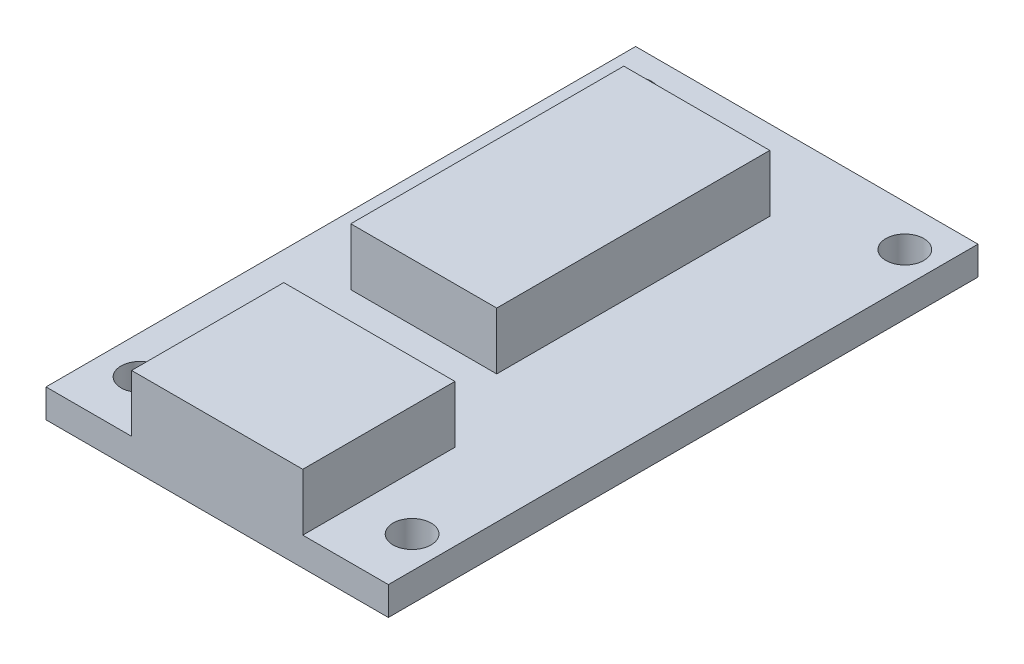
SolidWorks part; units mm, degrees
ref_plane "Front Plane" through (0, 0, 0) normal (0, 0, 1) x (1, 0, 0)
ref_plane "Top Plane" through (0, 0, 0) normal (0, 1, 0) x (1, 0, 0)
ref_plane "Right Plane" through (0, 0, 0) normal (1, 0, 0) x (0, 0, -1)
sketch "Sketch1" plane through (0, 0, 0) normal (0, 1, 0) x (1, 0, 0)
  line L1 (0, 0) -> (18, 0)
  line L2 (0, 0) -> (0, 31)
  line L3 (0, 31) -> (18, 31)
  line L4 (18, 0) -> (18, 31)
  line L5 (4.5, 0) -> (13.5, 0)
  line L6 (4.5, 0) -> (4.5, 8)
  line L7 (4.5, 8) -> (13.5, 8)
  line L8 (13.5, 0) -> (13.5, 8)
  point P9 (9, 8)
  point P10 (9, 31)
  dimension "D1" = 9
  dimension "D2" = 31
  dimension "D3" = 18
  dimension "D4" = 8
extrude "Boss-Extrude1" add sketch "Sketch1" along normal blind 1.5 contours L8 L1 L4 L3 L2 L6 L7 | L1 L8 L7 L6 region at (9, 0, -17.2037) region at (9, 0, -4)
extrude "Boss-Extrude2" add sketch "Sketch1<3>" along normal blind 4.5 contours L1 L8 L7 L6 region at (9, 0, -4)
sketch "Sketch1<3>" plane through (0, 0, 0) normal (0, 1, 0) x (1, 0, 0) same geometry as "Sketch1"
sketch "Sketch2" plane through (0, 1.5, 0) normal (0, 1, 0) x (1, 0, 0)
  line L1 (3.5837, 26.7947) -> (11.2572, 26.7947)
  line L2 (3.5837, 26.7947) -> (3.5837, 12.4392)
  line L3 (3.5837, 12.4392) -> (11.2572, 12.4392)
  line L4 (11.2572, 26.7947) -> (11.2572, 12.4392)
extrude "Boss-Extrude3" add sketch "Sketch2" along normal blind 3
sketch "Sketch3" plane through (0, 1.5, 0) normal (0, 1, 0) x (1, 0, 0)
  line L1 (2.0173, 28.8325) -> (16.3202, 28.8325)
  line L2 (2.0173, 28.8325) -> (2.0173, 2.9269)
  line L3 (2.0173, 2.9269) -> (16.3202, 2.9269)
  line L4 (16.3202, 28.8325) -> (16.3202, 2.9269)
  circle A0 centre (2.0173, 28.8325) radius 1
  circle A1 centre (2.0173, 2.9269) radius 1
  circle A2 centre (16.3202, 28.8325) radius 1
  circle A3 centre (16.3202, 2.9269) radius 1
  dimension "D1" = 2
extrude "Cut-Extrude1" cut sketch "Sketch3" against normal blind 10 contours L2 A1 L3 | L3 A1 L2 | L3 A3 L4 | L4 A3 L3 | L1 A0 L2 | L2 A0 L1 | L4 A2 L1 | L1 A2 L4 region at (1.8758, 1.5, -28.974) region at (2.4417, 1.5, -28.4081) region at (16.4617, 1.5, -28.974) region at (15.8958, 1.5, -28.4081) region at (2.4417, 1.5, -3.3513) region at (1.8758, 1.5, -2.7855) region at (16.4617, 1.5, -2.7855) region at (15.8958, 1.5, -3.3513)
